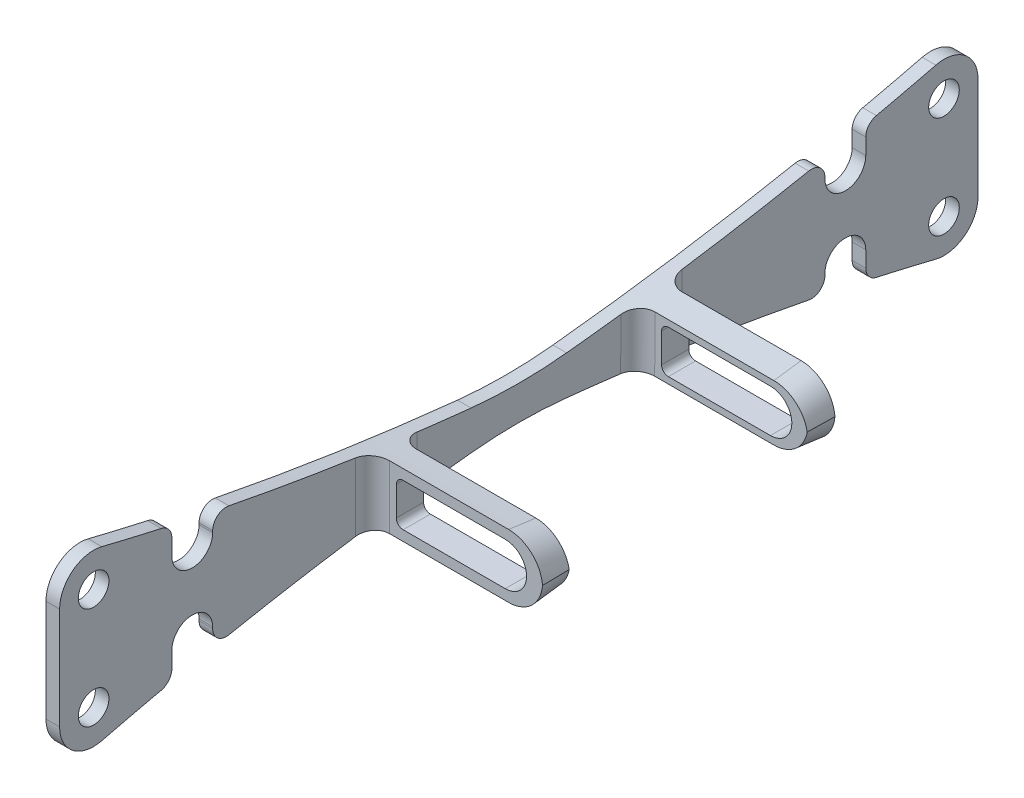
SolidWorks part; units mm, degrees
ref_plane "Alzado" through (0, 0, 0) normal (0, 0, 1) x (1, 0, 0)
ref_plane "Planta" through (0, 0, 0) normal (0, 1, 0) x (1, 0, 0)
ref_plane "Vista lateral" through (0, 0, 0) normal (1, 0, 0) x (0, 0, -1)
sketch "Croquis1" plane through (-11.5632, 0, 0) normal (1, 0, 0) x (0, 0, -1)
  line L0 (-487.5, 61.2) -> (-487.5, 76.2)
  line L1 (-352.5, 76.2) -> (-352.5, 61.2)
  arc A0 (-481.3016, 81.0543) -> (-487.5, 76.2) centre (-482.5, 76.2) ccw
  arc A1 (-487.5, 61.2) -> (-481.3015, 56.3458) centre (-482.5, 61.2) ccw
  arc A2 (-352.5, 76.2) -> (-358.6984, 81.0543) centre (-357.5, 76.2) ccw
  arc A3 (-358.6985, 56.3458) -> (-352.5, 61.2) centre (-357.5, 61.2) ccw
  arc A4 (-412.9782, 71.5632) -> (-358.6984, 81.0543) centre (-454.5713, 469.3948) ccw
  arc A5 (-481.3016, 81.0543) -> (-427.0138, 71.563) centre (-385.4331, 469.3959) ccw
  arc A6 (-427.0202, 65.838) -> (-481.3015, 56.3458) centre (-385.4216, -331.993) ccw
  arc A7 (-358.6985, 56.3458) -> (-412.9798, 65.838) centre (-454.5784, -331.993) ccw
  circle A8 centre (-420, -1.3) radius 67.504 construction
  circle A9 centre (-419.997, 138.6973) radius 67.5 construction
  arc A10 (-412.9798, 65.838) -> (-427.0202, 65.838) centre (-420, -1.3) ccw
  arc A11 (-427.0138, 71.563) -> (-412.9782, 71.5632) centre (-419.997, 138.6973) ccw
  dimension "D1" = 10
extrude "Saliente-Extruir1" add sketch "Croquis1" along normal blind 2
sketch "Croquis2" plane through (-9.5632, 0, 0) normal (1, 0, 0) x (0, 0, -1)
  line L0 (-471, 74.7) -> (-471, 78.6552)
  line L1 (-465, 74.7) -> (-465, 77.3894)
  line L2 (-471, 62.7) -> (-471, 58.7452)
  line L3 (-465, 62.7) -> (-465, 60.0111)
  line L5 (-375, 74.7) -> (-375, 77.3892)
  line L7 (-369, 74.7) -> (-369, 78.6551)
  line L9 (-375, 62.7) -> (-375, 60.0111)
  line L11 (-369, 62.7) -> (-369, 58.7452)
  arc A8 (-481.3016, 81.0543) -> (-427.0138, 71.563) centre (-385.4331, 469.3959) ccw construction
  circle A9 centre (-468, 74.7) radius 3
  arc A10 (-471, 74.7) -> (-465, 74.7) centre (-468, 74.7) ccw
  arc A11 (-427.0202, 65.838) -> (-481.3015, 56.3458) centre (-385.4216, -331.993) ccw construction
  arc A13 (-412.9782, 71.5632) -> (-358.6984, 81.0543) centre (-454.5713, 469.3948) ccw construction
  arc A15 (-358.6985, 56.3458) -> (-412.9798, 65.838) centre (-454.5784, -331.993) ccw construction
  arc A17 (-369, 58.7452) -> (-375, 60.0111) centre (-454.5784, -331.993) ccw
  arc A19 (-375, 77.3892) -> (-369, 78.6551) centre (-454.5713, 469.3948) ccw
  arc A21 (-465, 60.0111) -> (-471, 58.7452) centre (-385.4216, -331.993) ccw
  arc A23 (-471, 78.6552) -> (-465, 77.3894) centre (-385.4331, 469.3959) ccw
  circle A27 centre (-357.5, 61.2) radius 2.25
  circle A28 centre (-357.5, 61.2) radius 2.25
  circle A29 centre (-482.5, 61.2) radius 2.25
  circle A30 centre (-482.5, 61.2) radius 2.25
  circle A57 centre (-482.5, 76.2) radius 2.25
  circle A58 centre (-482.5, 76.2) radius 2.25
  circle A59 centre (-357.5, 76.2) radius 2.25
  circle A60 centre (-357.5, 76.2) radius 2.25
  circle A61 centre (-468, 62.7) radius 3
  arc A62 (-465, 62.7) -> (-471, 62.7) centre (-468, 62.7) ccw
  circle A65 centre (-372, 74.7) radius 3
  arc A66 (-375, 74.7) -> (-369, 74.7) centre (-372, 74.7) ccw
  circle A67 centre (-372, 62.7) radius 3
  arc A68 (-369, 62.7) -> (-375, 62.7) centre (-372, 62.7) ccw
  dimension "D1" = 0
  dimension "D10" = 0
  dimension "D11" = 0
  dimension "D25" = 0
  dimension "D26" = 0
  dimension "D27" = 0
  dimension "D30" = 0
  dimension "D31" = 0
extrude "Cortar-Extruir1" cut sketch "Croquis2" against normal blind 2
sketch "Croquis3" plane through (-9.5632, 0, 0) normal (1, 0, 0) x (0, 0, -1)
  line L0 (-441.5, 73.3448) -> (-441.5, 64.0565)
  line L1 (-437.5, 64.6023) -> (-437.5, 72.7991)
  line L2 (-487.5, 76.2) -> (-487.5, 61.2)
  line L3 (-352.5, 61.2) -> (-352.5, 76.2)
  line L6 (-419.996, 71.1973) -> (-420, 66.2041) construction
  line L7 (-402.5186, 64.6047) -> (-402.5055, 72.7979)
  line L8 (-398.5058, 73.3435) -> (-398.5207, 64.0594)
  line L19 (-369, 62.7) -> (-369, 58.7452)
  line L21 (-369, 78.6551) -> (-369, 74.7)
  line L23 (-375, 74.7) -> (-375, 77.3892)
  line L25 (-465, 77.3894) -> (-465, 74.7)
  line L27 (-471, 74.7) -> (-471, 78.6552)
  line L29 (-471, 58.7452) -> (-471, 62.7)
  line L31 (-465, 62.7) -> (-465, 60.0111)
  line L33 (-375, 60.0111) -> (-375, 62.7)
  arc A0 (-375, 60.0111) -> (-412.9798, 65.838) centre (-454.5784, -331.993) ccw construction
  arc A1 (-412.9782, 71.5632) -> (-375, 77.3892) centre (-454.5713, 469.3948) ccw construction
  arc A2 (-465, 77.3894) -> (-427.0138, 71.563) centre (-385.4331, 469.3959) ccw construction
  arc A3 (-398.5207, 64.0594) -> (-402.5186, 64.6047) centre (-454.5784, -331.993) ccw
  arc A4 (-402.5055, 72.7979) -> (-398.5058, 73.3435) centre (-454.5713, 469.3948) ccw
  arc A5 (-441.5, 73.3448) -> (-437.5, 72.7991) centre (-385.4331, 469.3959) ccw
  arc A10 (-369, 78.6551) -> (-358.6984, 81.0543) centre (-454.5713, 469.3948) ccw
  arc A11 (-427.0138, 71.563) -> (-412.9782, 71.5632) centre (-419.997, 138.6973) ccw
  arc A12 (-465, 77.3894) -> (-427.0138, 71.563) centre (-385.4331, 469.3959) ccw
  arc A13 (-481.3016, 81.0543) -> (-487.5, 76.2) centre (-482.5, 76.2) ccw
  arc A14 (-487.5, 61.2) -> (-481.3015, 56.3458) centre (-482.5, 61.2) ccw
  arc A15 (-471, 58.7452) -> (-481.3015, 56.3458) centre (-385.4216, -331.993) ccw
  arc A16 (-412.9798, 65.838) -> (-427.0202, 65.838) centre (-420, -1.3) ccw
  arc A17 (-375, 60.0111) -> (-412.9798, 65.838) centre (-454.5784, -331.993) ccw
  arc A18 (-358.6985, 56.3458) -> (-352.5, 61.2) centre (-357.5, 61.2) ccw
  arc A19 (-352.5, 76.2) -> (-358.6984, 81.0543) centre (-357.5, 76.2) ccw
  arc A38 (-358.6985, 56.3458) -> (-369, 58.7452) centre (-454.5784, -331.993) ccw
  arc A40 (-375, 74.7) -> (-369, 74.7) centre (-372, 74.7) ccw
  arc A42 (-412.9782, 71.5632) -> (-375, 77.3892) centre (-454.5713, 469.3948) ccw
  arc A44 (-471, 74.7) -> (-465, 74.7) centre (-468, 74.7) ccw
  arc A46 (-481.3016, 81.0543) -> (-471, 78.6552) centre (-385.4331, 469.3959) ccw
  arc A48 (-465, 62.7) -> (-471, 62.7) centre (-468, 62.7) ccw
  arc A50 (-427.0202, 65.838) -> (-465, 60.0111) centre (-385.4216, -331.993) ccw
  arc A51 (-437.5, 64.6023) -> (-441.5, 64.0565) centre (-385.4216, -331.993) ccw
  arc A52 (-369, 62.7) -> (-375, 62.7) centre (-372, 62.7) ccw
  dimension "D2" = 4
  dimension "D4" = 3.9988
  dimension "D1" = 0
extrude "Saliente-Extruir2" add sketch "Croquis3" along normal blind 25
fillet "Redondeo1" radius 5 4 edges at (15.4368, 64.3371, 400.519) (15.4368, 73.0656, 400.505) (15.4368, 73.0669, 439.5007) (15.4368, 64.3344, 439.5007)
fillet "Redondeo2" radius 2.5 4 edges at (-9.5632, 68.7014, 398.5133) (-9.5632, 68.7013, 402.5121) (-9.5632, 68.7007, 437.5) (-9.5632, 68.7006, 441.5)
sketch "Croquis4" plane through (0, 0, 441.5) normal (0, 0, 1) x (1, 0, 0)
  line L0 (9.9368, 71.8448) -> (-6.0632, 71.8448)
  line L1 (-6.0632, 71.8448) -> (-6.0632, 65.5565)
  line L2 (-6.0632, 65.5565) -> (9.9368, 65.5565)
  arc A0 (9.9368, 65.5565) -> (9.9368, 71.8448) centre (9.9368, 68.7006) ccw
  point P2 (1.8112, 71.8448)
  point P8 (1.8112, 65.5565)
  point P10 (3.9368, 67.7032)
  point P11 (3.9368, 69.6981)
  dimension "D1" = 16
extrude "Cortar-Extruir2" cut sketch "Croquis4" against normal blind 150
fillet "Redondeo3" radius 1 4 edges at (-6.0632, 65.5565, 400.5177) (-6.0632, 71.8448, 400.5076) (-6.0632, 65.5565, 439.5) (-6.0632, 71.8448, 439.5)
fillet "Redondeo4" radius 2 8 edges at (-10.5632, 78.6552, 471) (-10.5632, 77.3894, 465) (-10.5632, 58.7452, 471) (-10.5632, 60.0111, 465) (-10.5632, 60.0111, 375) (-10.5632, 58.7452, 369) (-10.5632, 77.3892, 375) (-10.5632, 78.6551, 369)
